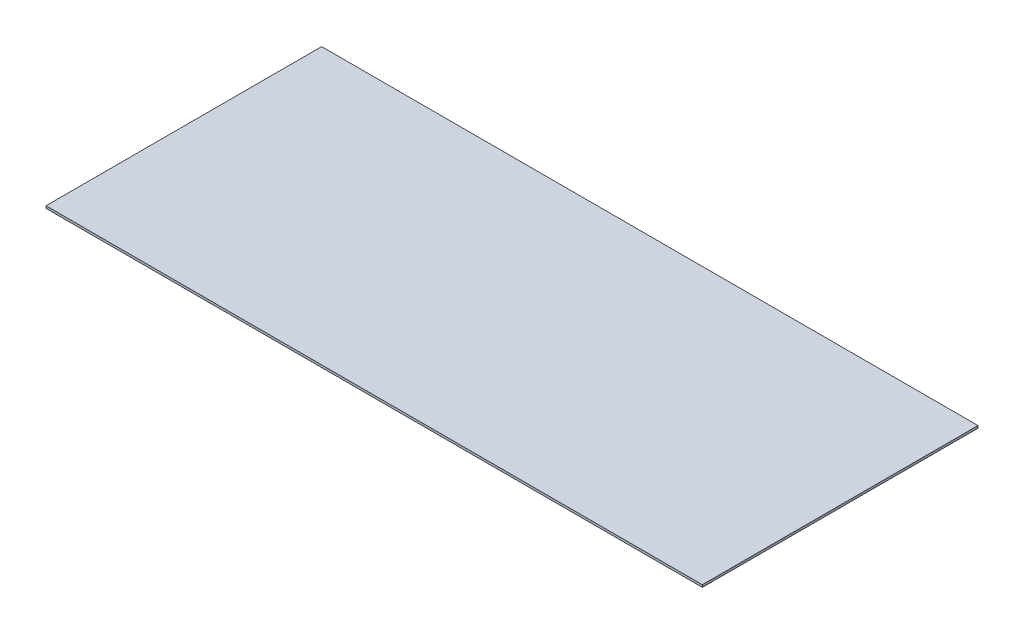
SolidWorks part; units mm, degrees
ref_plane "Front Plane" through (0, 0, 0) normal (0, 0, 1) x (1, 0, 0)
ref_plane "Top Plane" through (0, 0, 0) normal (0, 1, 0) x (1, 0, 0)
ref_plane "Right Plane" through (0, 0, 0) normal (1, 0, 0) x (0, 0, -1)
sketch "Sketch1" plane through (0, 0, 0) normal (0, 1, 0) x (1, 0, 0)
  line L1 (-446.0875, -187.325) -> (446.0875, -187.325)
  line L2 (-446.0875, -187.325) -> (-446.0875, 187.325)
  line L3 (-446.0875, 187.325) -> (446.0875, 187.325)
  line L4 (446.0875, -187.325) -> (446.0875, 187.325)
  line L5 (-446.0875, -187.325) -> (446.0875, 187.325) construction
  line L6 (-446.0875, 187.325) -> (446.0875, -187.325) construction
  point P0 (0, 0)
  dimension "D1" = 892.175
  dimension "D2" = 374.65
extrude "Boss-Extrude1" add sketch "Sketch1" along normal blind 3.175
